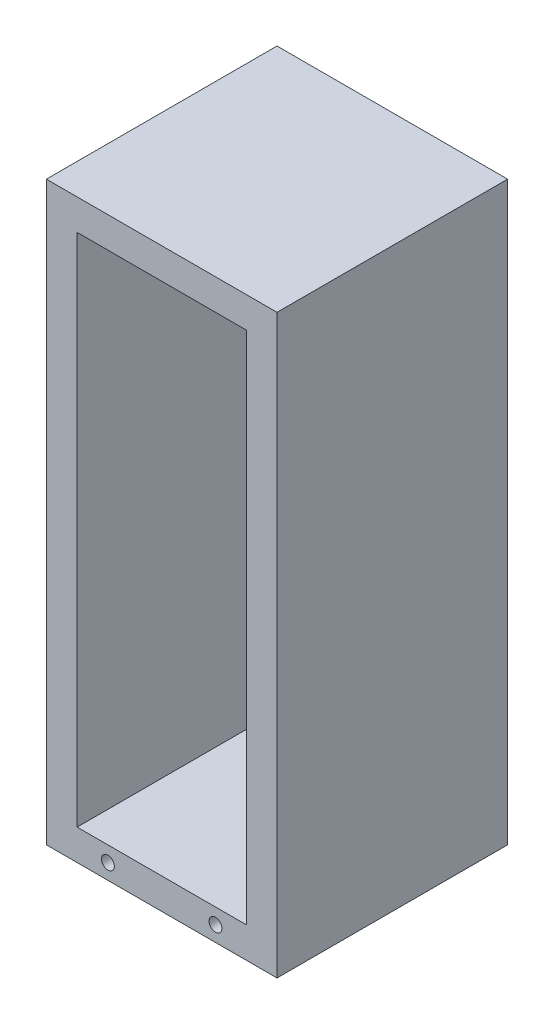
SolidWorks part; units mm, degrees
ref_plane "Front Plane" through (0, 0, 0) normal (0, 0, 1) x (1, 0, 0)
ref_plane "Top Plane" through (0, 0, 0) normal (0, 1, 0) x (1, 0, 0)
ref_plane "Right Plane" through (0, 0, 0) normal (1, 0, 0) x (0, 0, -1)
sketch "Sketch1" plane through (0, 0, 0) normal (0, 0, 1) x (1, 0, 0)
  line L1 (0, 0) -> (75, 0)
  line L2 (0, 0) -> (0, 187.5)
  line L3 (0, 187.5) -> (75, 187.5)
  line L4 (75, 0) -> (75, 187.5)
  line L5 (10, 10) -> (65, 10)
  line L6 (10, 10) -> (10, 177.5)
  line L7 (10, 177.5) -> (65, 177.5)
  line L8 (65, 10) -> (65, 177.5)
  dimension "D1" = 75
  dimension "D2" = 187.5
  dimension "D3" = 10
  dimension "D4" = 10
  dimension "D5" = 10
  dimension "D6" = 10
extrude "Boss-Extrude1" add sketch "Sketch1" against normal blind 75
sketch "Sketch2" plane through (0, 0, 0) normal (0, 0, 1) x (1, 0, 0)
  line L0 (0, 5) -> (75, 5) construction
  line L3 (10, 10) -> (65, 10) construction
  line L4 (37.5, 10) -> (37.5, 0) construction
  line L5 (0, 0) -> (75, 0) construction
  line L8 (0, 187.5) -> (0, 0) construction
  line L9 (75, 0) -> (75, 187.5) construction
  circle A0 centre (20, 5) radius 2
  circle A1 centre (55, 5) radius 2
  dimension "D3" = 4
  dimension "D1" = 5
  dimension "D2" = 17.5
ref_plane "Plane1" through (0, 0, -37.5) normal (0, 0, 1) x (1, 0, 0)
hole_wizard "Tap Drill for M5x0.8 Tap1" positions "Sketch3" profile "Sketch4" hole size "M5x0.8" standard "ANSI Metric"
sketch "Sketch3" plane through (0, 0, 0) normal (0, 0, 1) x (1, 0, 0)
  point P0 (20, 5)
  point P3 (55, 5)
sketch "Sketch4" plane through (20, 5, 0) normal (1, 0, 0) x (0, -1, 0)
  line L0 (0, 0) -> (0, 8.9618)
  line L1 (0, 8.9618) -> (2.1, 7.7)
  line L2 (2.1, 7.7) -> (2.1, 0)
  line L5 (2.1, 0) -> (0, 0)
  line L10 (0, 8.9618) -> (-2.1, 7.7) construction
  line L11 (0, -6.35) -> (0, 107.95) construction
  dimension "Hole Dia." = 4.2
  dimension "Hole Depth" = 7.7
  dimension "Drill Angle" = 118
mirror "Mirror1" about plane through (0, 0, -37.5) normal (0, 0, 1) of "Tap Drill for M5x0.8 Tap1"
hole_wizard "Tap Drill for M5x0.8 Tap2" positions "Sketch8" profile "Sketch9" hole size "M5x0.8" standard "ANSI Metric" end condition through all
sketch "Sketch8" plane through (0, 10, 0) normal (0, 1, 0) x (1, 0, 0)
  line L0 (37.5, 75) -> (37.5, 0) construction
  line L1 (10, 75) -> (65, 75) construction
  line L2 (10, 0) -> (65, 0) construction
  point P0 (37.5, 37.5)
  point P10 (0, 0)
  point P11 (37.5, 37.5)
sketch "Sketch9" plane through (37.5, 10, -37.5) normal (1, 0, 0) x (0, 0, 1)
  line L0 (0, 0) -> (0, 10)
  line L1 (0, 10) -> (2.1, 10)
  line L2 (2.1, 10) -> (2.1, 0)
  line L5 (2.1, 0) -> (0, 0)
  line L11 (0, -6.35) -> (0, 107.95) construction
  dimension "Thru Hole Dia." = 4.2
  dimension "Thru Hole Depth" = 10
